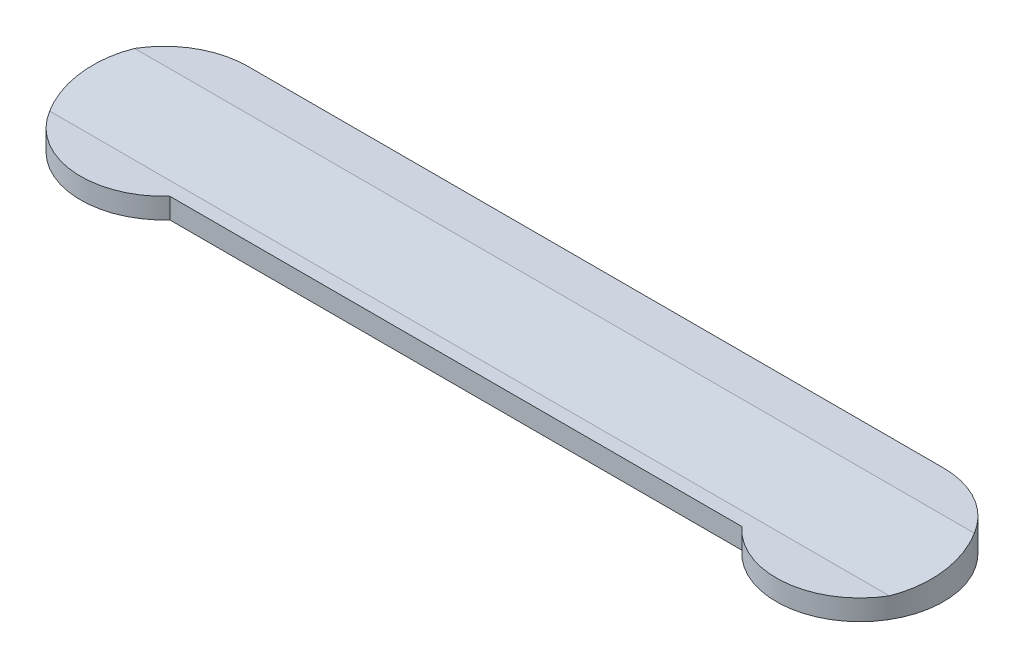
SolidWorks part; units mm, degrees
ref_plane "Front Plane" through (0, 0, 0) normal (0, 0, 1) x (1, 0, 0)
ref_plane "Top Plane" through (0, 0, 0) normal (0, 1, 0) x (1, 0, 0)
ref_plane "Right Plane" through (0, 0, 0) normal (1, 0, 0) x (0, 0, -1)
sketch "Sketch1" plane through (0, 0, 0) normal (0, 1, 0) x (1, 0, 0)
  line L1 (72, -30.5) -> (-72, -30.5) construction
  line L3 (212.5, 30.5) -> (-41.5, 30.5)
  line L5 (72, -30.5) -> (-72, 30.5) construction
  line L6 (72, 30.5) -> (-11.3836, -4.8222) construction
  line L7 (-18.9168, -20.5) -> (189.9168, -20.5)
  line L8 (-58.9884, -24.9881) -> (-72, -30.5) construction
  arc A0 (-41.5, 30.5) -> (-18.9168, -20.5) centre (-41.5, 0) ccw
  arc A1 (189.9168, -20.5) -> (212.5, 30.5) centre (212.5, 0) ccw
  point P0 (0, 0)
  dimension "D4" = 61
  dimension "D2" = 254
  dimension "D1" = 144
  dimension "D3" = 61
  dimension "D6" = 10
extrude "Boss-Extrude1" add sketch "Sketch1" along normal blind 15
sketch "Sketch3" plane through (0, 0, 0) normal (1, 0, 0) x (0, 0, -1)
  line L0 (-30.5, 7.5) -> (-15.5, 7.5)
  line L1 (-30.5, 15) -> (-30.5, 0) construction
  line L2 (30.5, 11.8179) -> (15.5, 11.8179)
  line L3 (30.5, 15) -> (30.5, 0) construction
  line L4 (15.5, 11.8179) -> (-15.5, 7.5)
  line L5 (-30.5, 7.5) -> (-30.5, 24.9443)
  line L6 (-30.5, 24.9443) -> (30.5, 24.9443)
  line L7 (30.5, 24.9443) -> (30.5, 11.8179)
  dimension "D1" = 15
  dimension "D2" = 15
extrude "Cut-Extrude2" cut sketch "Sketch3" along normal through all both and the other way through all
sketch "Sketch2" plane through (0, 0, 0) normal (0, 1, 0) x (1, 0, 0)
  line L6 (212.5, 25.5) -> (-41.5, 25.5)
  line L7 (-21.2515, -15.5) -> (192.2515, -15.5)
  line L8 (212.5, 25.5) -> (-41.5, 25.5)
  line L9 (-21.2515, -15.5) -> (192.2515, -15.5)
  arc A8 (192.2515, -15.5) -> (212.5, 25.5) centre (212.5, 0) ccw
  arc A9 (-41.5, 25.5) -> (-21.2515, -15.5) centre (-41.5, 0) ccw
  arc A10 (192.2515, -15.5) -> (212.5, 25.5) centre (212.5, 0) ccw
  arc A11 (-41.5, 25.5) -> (-21.2515, -15.5) centre (-41.5, 0) ccw
  dimension "D1" = 5
extrude "Cut-Extrude3" cut sketch "Sketch2" along normal blind 5
sketch "Sketch4" plane through (0, 0, 0) normal (1, 0, 0) x (0, 0, -1)
  line L0 (25.5, 5) -> (25.5, 9.3179)
  line L1 (25.5, 9.3179) -> (15.5, 9.3179)
  line L2 (15.5, 9.3179) -> (-15.5, 5)
  line L3 (-15.5, 5) -> (25.5, 5)
  line L4 (30.5, 11.8179) -> (15.5, 11.8179) construction
  line L5 (-15.5, 7.5) -> (-30.5, 7.5) construction
  line L6 (15.5, 11.8179) -> (-15.5, 7.5) construction
  dimension "D1" = 2.5
  dimension "D2" = 2.5
  dimension "D3" = 2.4761
extrude "Cut-Extrude4" cut sketch "Sketch4" along normal blind 192.302 and the other way blind 21
fillet "Fillet1" radius 6.35 1 edges at (85.651, 9.3179, -15.5)
sketch "Sketch5" plane through (0, 0, -30.5) normal (0, 0, -1) x (-1, 0, 0)
  line L1 (33.55, 0) -> (-33.55, 0) construction
  line L2 (-212.5, 11.8179) -> (-212.5, 0) construction
  circle A3 centre (-161.7, 0) radius 5.08
  circle A4 centre (-110.9, 0) radius 5.08
  circle A5 centre (-60.1, 0) radius 5.08
  circle A6 centre (-9.3, 0) radius 5.08
  dimension "D1" = 50.8
  dimension "D2" = 50.8
  dimension "D3" = 50.8
  dimension "D4" = 50.8
extrude "Cut-Extrude5" cut sketch "Sketch5" against normal blind 7.62
